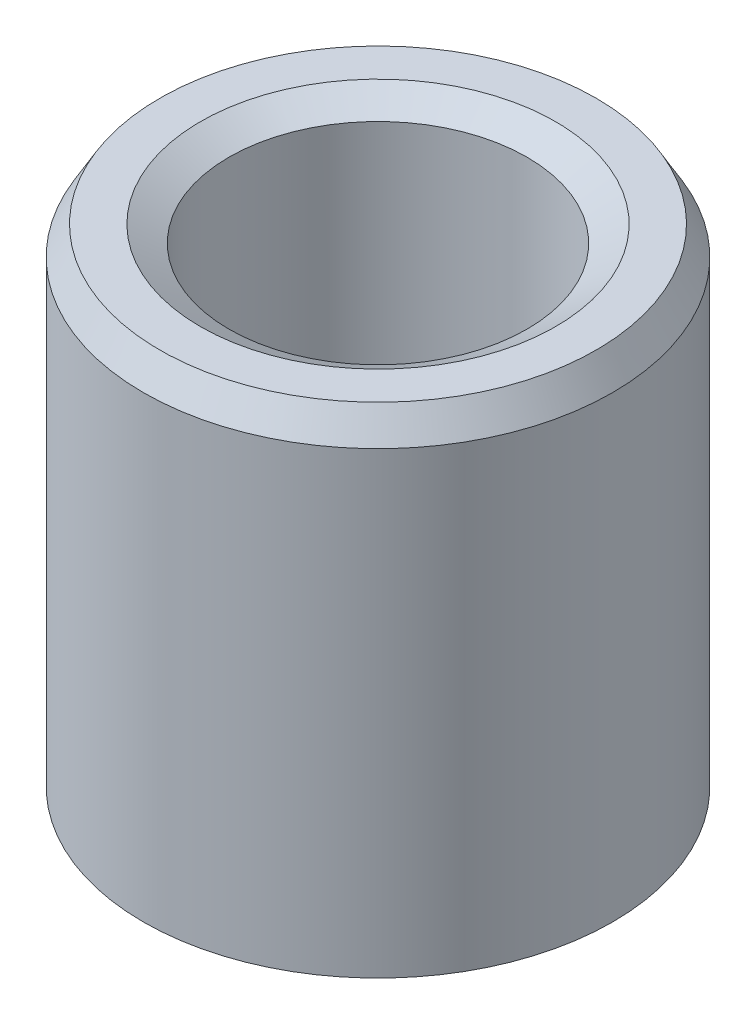
SolidWorks part; units mm, degrees
ref_plane "Front Plane" through (0, 0, 0) normal (0, 0, 1) x (1, 0, 0)
ref_plane "Top Plane" through (0, 0, 0) normal (0, 1, 0) x (1, 0, 0)
ref_plane "Right Plane" through (0, 0, 0) normal (1, 0, 0) x (0, 0, -1)
sketch "Sketch1" plane through (0, 0, 0) normal (0, 1, 0) x (1, 0, 0)
  circle A0 centre (0, 0) radius 7.5
  dimension "SLEEVE_OD" = 15
extrude "Boss-Extrude1" add sketch "Sketch1" along normal blind 16.0942
sketch "Sketch2" plane through (0, 0, 0) normal (0, 1, 0) x (1, 0, 0)
  circle A0 centre (0, 0) radius 4.7627
  dimension "BORE_D" = 9.5254
extrude "Cut-Extrude1" cut sketch "Sketch2" along normal through all
chamfer "Chamfer1" distance 0.913 angle 30 4 edges at (0, 16.0942, 4.7627) (0, 0, 4.7627) (0, 0, 7.5) (0, 16.0942, 7.5) first distance on face at (0, 16.0942, 4.7627) first distance on face at (0, 0, 4.7627) first distance on face at (0, 16.0942, 7.5)
